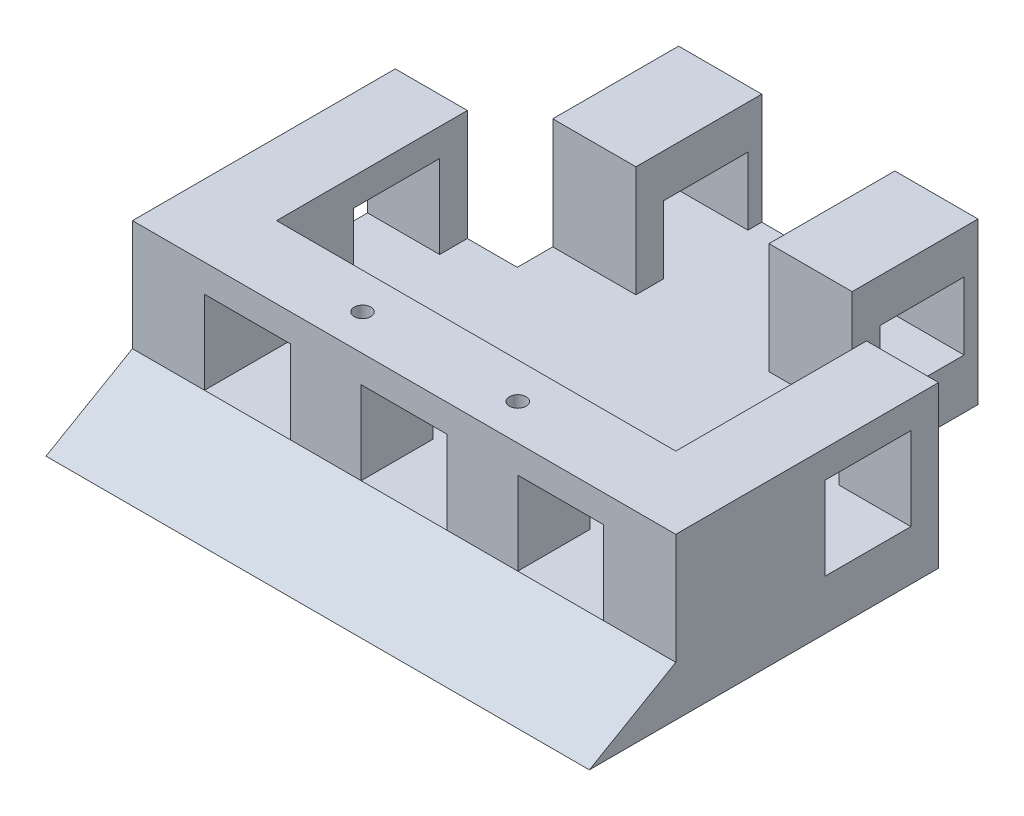
SolidWorks part; units mm, degrees
ref_plane "Alzado" through (0, 0, 0) normal (0, 0, 1) x (1, 0, 0)
ref_plane "Planta" through (0, 0, 0) normal (0, 1, 0) x (1, 0, 0)
ref_plane "Vista lateral" through (0, 0, 0) normal (1, 0, 0) x (0, 0, -1)
sketch "Croquis1" plane through (0, 0, 0) normal (0, 1, 0) x (1, 0, 0)
  line L1 (-49, -49) -> (49, -49)
  line L2 (-49, -49) -> (-49, 49)
  line L3 (-49, 49) -> (49, 49)
  line L4 (49, -49) -> (49, 49)
  line L5 (-49, -49) -> (49, 49) construction
  line L6 (-49, 49) -> (49, -49) construction
  point P0 (0, 0)
  dimension "D1" = 98
  dimension "D2" = 98
extrude "Saliente-Extruir1" add sketch "Croquis1" along normal blind 9
chamfer "Chaflán1" distance 9 angle 60 1 edges at (0, 9, 49) first distance on face at (0, 4.5, 49)
sketch "Croquis2" plane through (0, 9, 0) normal (0, 1, 0) x (1, 0, 0)
  line L5 (-49, 49) -> (-27, 49)
  line L6 (-49, 49) -> (-49, 14)
  line L7 (-49, 14) -> (-27, 14)
  line L8 (-27, 49) -> (-27, 14)
  line L9 (49, 49) -> (27, 49)
  line L10 (49, 49) -> (49, 14)
  line L11 (49, 14) -> (27, 14)
  line L12 (27, 49) -> (27, 14)
  dimension "D1" = 22
  dimension "D2" = 35
  dimension "D3" = 22
  dimension "D4" = 35
extrude "Cortar-Extruir1" cut sketch "Croquis2" against normal blind 9
sketch "Croquis3" plane through (0, 9, 0) normal (0, 1, 0) x (1, 0, 0)
  line L0 (27, 49) -> (27, 14) construction
  line L1 (27, 40.6) -> (12, 40.6)
  line L3 (27, 25.4) -> (12, 25.4)
  line L5 (-27, 14) -> (-27, 49) construction
  line L6 (-27, 40.6) -> (-12, 40.6)
  line L8 (-27, 25.4) -> (-12, 25.4)
  line L17 (-27, 22.9) -> (-12, 22.9)
  line L19 (-27, 43.1) -> (-12, 43.1)
  line L20 (-27, 40.6) -> (-27, 43.1)
  line L21 (-27, 25.4) -> (-27, 22.9)
  line L22 (-29.5, 22.9) -> (-9.5, 22.9) construction
  line L23 (-29.5, 43.1) -> (-29.5, 22.9) construction
  line L24 (-29.5, 43.1) -> (-9.5, 43.1) construction
  line L25 (-27, 40.6) -> (-27, 25.4) construction
  line L26 (-12, 40.6) -> (-12, 25.4) construction
  line L27 (-9.5, 43.1) -> (-9.5, 22.9) construction
  line L28 (-12, 40.6) -> (-12, 43.1)
  line L29 (-12, 25.4) -> (-12, 22.9)
  line L31 (27, 22.9) -> (12, 22.9)
  line L33 (27, 43.1) -> (12, 43.1)
  line L34 (9.5, 43.1) -> (9.5, 22.9) construction
  line L35 (12, 40.6) -> (12, 25.4) construction
  line L36 (27, 40.6) -> (27, 25.4) construction
  line L37 (29.5, 43.1) -> (29.5, 22.9) construction
  line L38 (27, 40.6) -> (27, 43.1)
  line L39 (12, 40.6) -> (12, 43.1)
  line L40 (12, 25.4) -> (12, 22.9)
  line L41 (27, 25.4) -> (27, 22.9)
  line L42 (29.5, 43.1) -> (9.5, 43.1) construction
  line L43 (29.5, 22.9) -> (9.5, 22.9) construction
  dimension "D1" = 15.2
  dimension "D3" = 15
  dimension "D4" = 15.2
  dimension "D5" = 15
  dimension "D6" = 2.5
  dimension "D7" = 2.5
extrude "Saliente-Extruir2" add sketch "Croquis3" along normal blind 12.2
sketch "Croquis4" plane through (0, 21.2, 0) normal (0, 1, 0) x (1, 0, 0)
  line L1 (-27, 22.9) -> (-12, 22.9)
  line L2 (-27, 22.9) -> (-27, 43.1)
  line L3 (-27, 43.1) -> (-12, 43.1)
  line L4 (-12, 22.9) -> (-12, 43.1)
  line L5 (12, 43.1) -> (27, 43.1)
  line L6 (12, 43.1) -> (12, 22.9)
  line L7 (12, 22.9) -> (27, 22.9)
  line L8 (27, 43.1) -> (27, 22.9)
extrude "Saliente-Extruir3" add sketch "Croquis4" along normal blind 2.5
sketch "Croquis5" plane through (27, 0, 0) normal (1, 0, 0) x (0, 0, -1)
  line L1 (43.1, 9) -> (49, 9)
  line L2 (43.1, 9) -> (43.1, 0)
  line L3 (43.1, 0) -> (49, 0)
  line L4 (49, 9) -> (49, 0)
extrude "Cortar-Extruir2" cut sketch "Croquis5" against normal blind 54.2
sketch "Croquis6" plane through (0, 0, -22.9) normal (0, 0, 1) x (1, 0, 0)
  line L1 (-27, 23.7) -> (-12, 23.7)
  line L2 (-27, 23.7) -> (-27, 9)
  line L3 (-27, 9) -> (-12, 9)
  line L4 (-12, 23.7) -> (-12, 9)
  line L5 (12, 23.7) -> (27, 23.7)
  line L6 (12, 23.7) -> (12, 9)
  line L7 (12, 9) -> (27, 9)
  line L8 (27, 23.7) -> (27, 9)
extrude "Saliente-Extruir4" add sketch "Croquis6" along normal blind 2.5
sketch "Croquis7" plane through (0, 9, 0) normal (0, 1, 0) x (1, 0, 0)
  line L0 (-49, 14) -> (-49, -33.4115)
  line L1 (-49, -33.4115) -> (49, -33.4115)
  line L2 (49, -33.4115) -> (49, 14)
  line L3 (-36, 14) -> (-36, -20.4115)
  line L4 (-36, -20.4115) -> (36, -20.4115)
  line L5 (36, -20.4115) -> (36, 14)
  line L6 (49, 14) -> (36, 14)
  line L7 (-36, 14) -> (-49, 14)
  dimension "D1" = 13
extrude "Saliente-Extruir5" add sketch "Croquis7" along normal blind 20
sketch "Croquis8" plane through (49, 0, 0) normal (1, 0, 0) x (0, 0, -1)
  line L0 (20.4, 9) -> (14, 9) construction
  line L1 (-6.5, 9) -> (9, 9)
  line L2 (-6.5, 9) -> (-6.5, 24)
  line L3 (-6.5, 24) -> (9, 24)
  line L4 (9, 9) -> (9, 24)
  line L5 (14, 0) -> (14, 29) construction
  dimension "D1" = 15.5
  dimension "D2" = 15
  dimension "D3" = 5
extrude "Cortar-Extruir3" cut sketch "Croquis8" against normal blind 98
sketch "Croquis9" plane through (0, 0, 33.4115) normal (0, 0, 1) x (1, 0, 0)
  line L0 (-49, 9) -> (49, 9) construction
  line L1 (-36, 9) -> (-20.5, 9)
  line L2 (-36, 9) -> (-36, 24)
  line L3 (-36, 24) -> (-20.5, 24)
  line L4 (-20.5, 9) -> (-20.5, 24)
  line L5 (49, 29) -> (49, 9) construction
  line L6 (-7.75, 9) -> (7.75, 9)
  line L7 (-7.75, 9) -> (-7.75, 24)
  line L8 (-7.75, 24) -> (7.75, 24)
  line L9 (7.75, 9) -> (7.75, 24)
  line L10 (20.5, 9) -> (36, 9)
  line L11 (20.5, 9) -> (20.5, 24)
  line L12 (20.5, 24) -> (36, 24)
  line L13 (36, 9) -> (36, 24)
  line L14 (-49, 29) -> (-49, 9) construction
  point P18 (0, 24)
  dimension "D1" = 13
  dimension "D2" = 13
  dimension "D3" = 15.5
  dimension "D4" = 15.5
  dimension "D5" = 15.5
  dimension "D6" = 20.5
  dimension "D7" = 15
  dimension "D8" = 15
  dimension "D9" = 15
extrude "Cortar-Extruir4" cut sketch "Croquis9" against normal blind 13
sketch "Croquis10" plane through (0, 23.7, 0) normal (0, 1, 0) x (1, 0, 0)
  line L1 (-27, 43.1) -> (-12, 43.1)
  line L2 (-27, 43.1) -> (-27, 20.4)
  line L3 (-27, 20.4) -> (-12, 20.4)
  line L4 (-12, 43.1) -> (-12, 20.4)
  line L5 (12, 43.1) -> (27, 43.1)
  line L6 (12, 43.1) -> (12, 20.4)
  line L7 (12, 20.4) -> (27, 20.4)
  line L8 (27, 43.1) -> (27, 20.4)
extrude "Saliente-Extruir6" add sketch "Croquis10" along normal blind 5.3
sketch "Croquis11" plane through (0, 29, 0) normal (0, 1, 0) x (1, 0, 0)
  line L6 (-49, 14) -> (-49, -33.4115) construction
  line L7 (49, -33.4115) -> (49, 14) construction
  line L9 (-36, -33.4115) -> (36, -33.4115) construction
  line L12 (36, -20.4115) -> (-36, -20.4115) construction
  circle A0 centre (-14, -26.9115) radius 1.5
  circle A1 centre (14, -26.9115) radius 1.5
  dimension "D5" = 3
  dimension "D6" = 3
  dimension "D7" = 6.5
  dimension "D8" = 6.5
  dimension "D9" = 35
  dimension "D10" = 35
  dimension "D3" = 13
  dimension "D4" = 13
extrude "Cortar-Extruir5" cut sketch "Croquis11" against normal blind 10
